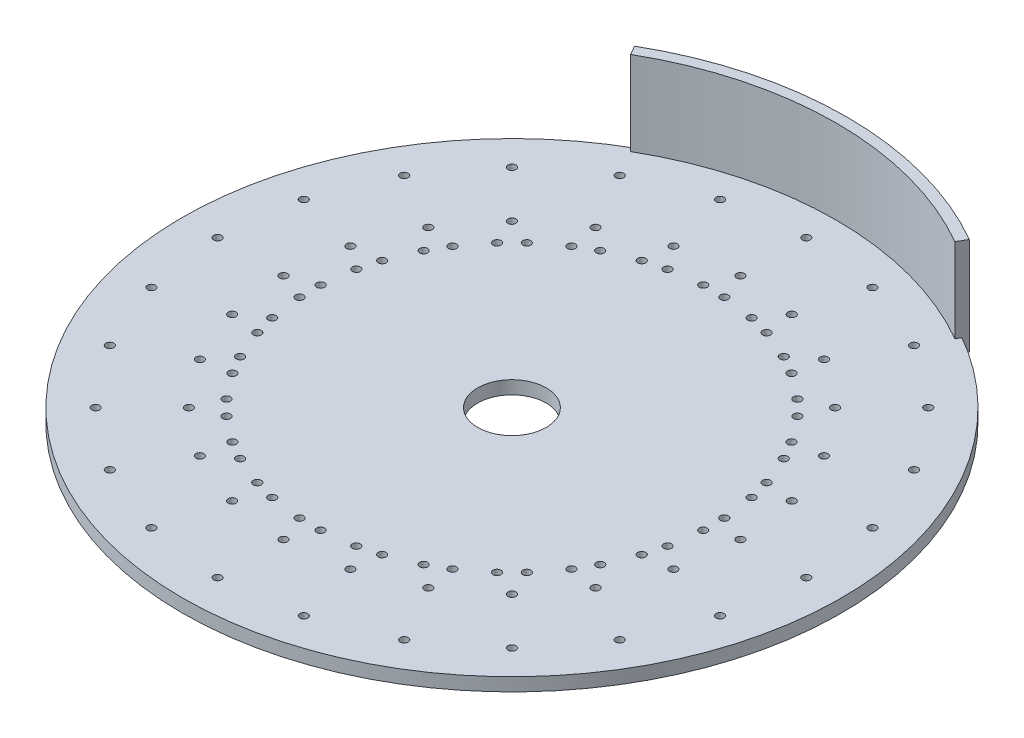
SolidWorks part; units mm, degrees
note: The reader was unsure of these and kept them because the rebuilt part matched: shared geometry of "Sketch2<3>".
material "ABS PC"
ref_plane "Front Plane" through (0, 0, 0) normal (0, 0, 1) x (1, 0, 0)
ref_plane "Top Plane" through (0, 0, 0) normal (0, 1, 0) x (1, 0, 0)
ref_plane "Right Plane" through (0, 0, 0) normal (1, 0, 0) x (0, 0, -1)
sketch "Sketch1" plane through (0, 0, 0) normal (0, 1, 0) x (1, 0, 0)
  line L0 (0, 0) -> (0, 145.2031) construction
  line L1 (0, 0) -> (86.65, 0) construction
  circle A0 centre (0, 0) radius 125
  circle A1 centre (0, 0) radius 76.652 construction
  circle A2 centre (0, 76.652) radius 2.5 construction
  circle A3 centre (21.001, 74.9318) radius 2.5 construction
  circle A4 centre (40.8412, 67.8347) radius 2.5 construction
  circle A5 centre (58.1686, 55.8445) radius 2.5 construction
  circle A6 centre (71.8022, 39.7782) radius 2.5 construction
  circle A7 centre (80.813, 20.7307) radius 2.5 construction
  circle A8 centre (84.5868, 0) radius 2.5 construction
  circle A9 centre (82.8667, -21.001) radius 2.5 construction
  circle A10 centre (75.7696, -40.8412) radius 2.5 construction
  circle A11 centre (63.7794, -58.1686) radius 2.5 construction
  circle A12 centre (47.713, -71.8022) radius 2.5 construction
  circle A13 centre (28.6655, -80.813) radius 2.5 construction
  circle A14 centre (7.9349, -84.5868) radius 2.5 construction
  circle A15 centre (-13.0662, -82.8667) radius 2.5 construction
  circle A16 centre (-32.9064, -75.7696) radius 2.5 construction
  circle A17 centre (-50.2337, -63.7794) radius 2.5 construction
  circle A18 centre (-63.8673, -47.713) radius 2.5 construction
  circle A19 centre (-72.8781, -28.6655) radius 2.5 construction
  circle A20 centre (-76.652, -7.9349) radius 2.5 construction
  circle A21 centre (-74.9318, 13.0662) radius 2.5 construction
  circle A22 centre (-67.8347, 32.9064) radius 2.5 construction
  circle A23 centre (-55.8445, 50.2337) radius 2.5 construction
  circle A24 centre (-39.7782, 63.8673) radius 2.5 construction
  circle A25 centre (-20.7307, 72.8781) radius 2.5 construction
  circle A26 centre (-4, 76.5475) radius 1.5
  circle A27 centre (4, 76.5475) radius 1.5
  circle A28 centre (15.9483, 74.9745) radius 1.5
  circle A29 centre (23.6757, 72.904) radius 1.5
  circle A30 centre (34.8097, 68.2921) radius 1.5
  circle A31 centre (41.7379, 64.2921) radius 1.5
  circle A32 centre (51.2989, 56.9557) radius 1.5
  circle A33 centre (56.9557, 51.2989) radius 1.5
  circle A34 centre (64.2921, 41.7379) radius 1.5
  circle A35 centre (68.2921, 34.8097) radius 1.5
  circle A36 centre (72.904, 23.6757) radius 1.5
  circle A37 centre (74.9745, 15.9483) radius 1.5
  circle A38 centre (76.5475, 4) radius 1.5
  circle A39 centre (76.5475, -4) radius 1.5
  circle A40 centre (74.9745, -15.9483) radius 1.5
  circle A41 centre (72.904, -23.6757) radius 1.5
  circle A42 centre (68.2921, -34.8097) radius 1.5
  circle A43 centre (64.2921, -41.7379) radius 1.5
  circle A44 centre (56.9557, -51.2989) radius 1.5
  circle A45 centre (51.2989, -56.9557) radius 1.5
  circle A46 centre (41.7379, -64.2921) radius 1.5
  circle A47 centre (34.8097, -68.2921) radius 1.5
  circle A48 centre (23.6757, -72.904) radius 1.5
  circle A49 centre (15.9483, -74.9745) radius 1.5
  circle A50 centre (4, -76.5475) radius 1.5
  circle A51 centre (-4, -76.5475) radius 1.5
  circle A52 centre (-15.9483, -74.9745) radius 1.5
  circle A53 centre (-23.6757, -72.904) radius 1.5
  circle A54 centre (-34.8097, -68.2921) radius 1.5
  circle A55 centre (-41.7379, -64.2921) radius 1.5
  circle A56 centre (-51.2989, -56.9557) radius 1.5
  circle A57 centre (-56.9557, -51.2989) radius 1.5
  circle A58 centre (-64.2921, -41.7379) radius 1.5
  circle A59 centre (-68.2921, -34.8097) radius 1.5
  circle A60 centre (-72.904, -23.6757) radius 1.5
  circle A61 centre (-74.9745, -15.9483) radius 1.5
  circle A62 centre (-76.5475, -4) radius 1.5
  circle A63 centre (-76.5475, 4) radius 1.5
  circle A64 centre (-74.9745, 15.9483) radius 1.5
  circle A65 centre (-72.904, 23.6757) radius 1.5
  circle A66 centre (-68.2921, 34.8097) radius 1.5
  circle A67 centre (-64.2921, 41.7379) radius 1.5
  circle A68 centre (-56.9557, 51.2989) radius 1.5
  circle A69 centre (-51.2989, 56.9557) radius 1.5
  circle A70 centre (-41.7379, 64.2921) radius 1.5
  circle A71 centre (-34.8097, 68.2921) radius 1.5
  circle A72 centre (-23.6757, 72.904) radius 1.5
  circle A73 centre (-15.9483, 74.9745) radius 1.5
  circle A74 centre (0, 0) radius 13
  circle A75 centre (86.65, 0) radius 1.5
  circle A76 centre (111.65, 0) radius 1.5
  circle A77 centre (107.8456, -28.8971) radius 1.5
  circle A78 centre (96.6917, -55.825) radius 1.5
  circle A79 centre (78.9485, -78.9485) radius 1.5
  circle A80 centre (55.825, -96.6917) radius 1.5
  circle A81 centre (28.8971, -107.8456) radius 1.5
  circle A82 centre (0, -111.65) radius 1.5
  circle A83 centre (-28.8971, -107.8456) radius 1.5
  circle A84 centre (-55.825, -96.6917) radius 1.5
  circle A85 centre (-78.9485, -78.9485) radius 1.5
  circle A86 centre (-96.6917, -55.825) radius 1.5
  circle A87 centre (-107.8456, -28.8971) radius 1.5
  circle A88 centre (-111.65, 0) radius 1.5
  circle A89 centre (-107.8456, 28.8971) radius 1.5
  circle A90 centre (-96.6917, 55.825) radius 1.5
  circle A91 centre (-78.9485, 78.9485) radius 1.5
  circle A92 centre (-55.825, 96.6917) radius 1.5
  circle A93 centre (-28.8971, 107.8456) radius 1.5
  circle A94 centre (0, 111.65) radius 1.5
  circle A95 centre (28.8971, 107.8456) radius 1.5
  circle A96 centre (55.825, 96.6917) radius 1.5
  circle A97 centre (78.9485, 78.9485) radius 1.5
  circle A98 centre (96.6917, 55.825) radius 1.5
  circle A99 centre (107.8456, 28.8971) radius 1.5
  circle A100 centre (0, 0) radius 111.65 construction
  circle A101 centre (0, 0) radius 81.1 construction
  circle A103 centre (83.6975, -22.4267) radius 1.5
  circle A104 centre (75.0411, -43.325) radius 1.5
  circle A105 centre (61.2708, -61.2708) radius 1.5
  circle A106 centre (43.325, -75.0411) radius 1.5
  circle A107 centre (22.4267, -83.6975) radius 1.5
  circle A108 centre (0, -86.65) radius 1.5
  circle A109 centre (-22.4267, -83.6975) radius 1.5
  circle A110 centre (-43.325, -75.0411) radius 1.5
  circle A111 centre (-61.2708, -61.2708) radius 1.5
  circle A112 centre (-75.0411, -43.325) radius 1.5
  circle A113 centre (-83.6975, -22.4267) radius 1.5
  circle A114 centre (-86.65, 0) radius 1.5
  circle A115 centre (-83.6975, 22.4267) radius 1.5
  circle A116 centre (-75.0411, 43.325) radius 1.5
  circle A117 centre (-61.2708, 61.2708) radius 1.5
  circle A118 centre (-43.325, 75.0411) radius 1.5
  circle A119 centre (-22.4267, 83.6975) radius 1.5
  circle A120 centre (0, 86.65) radius 1.5
  circle A121 centre (22.4267, 83.6975) radius 1.5
  circle A122 centre (43.325, 75.0411) radius 1.5
  circle A123 centre (61.2708, 61.2708) radius 1.5
  circle A124 centre (75.0411, 43.325) radius 1.5
  circle A125 centre (83.6975, 22.4267) radius 1.5
  circle A126 centre (0, 222.5) radius 5 construction
  circle A127 centre (192.6907, 111.25) radius 5 construction
  circle A128 centre (192.6907, -111.25) radius 5 construction
  circle A129 centre (0, -222.5) radius 5 construction
  circle A130 centre (-192.6907, -111.25) radius 5 construction
  circle A131 centre (-192.6907, 111.25) radius 5 construction
  point P55 (3.9674, -3.9674)
  point P152 (0, 0)
  point P205 (0, 0)
  point P265 (0, 0)
  dimension "D1" = 250
  dimension "D2" = 5
  dimension "D4" = 8
  dimension "D5" = 3
  dimension "D7" = 26
  dimension "D8" = 86.65
  dimension "D9" = 3
  dimension "D10" = 222.5
  dimension "D11" = 24
  dimension "D12" = 223.3
  dimension "D13" = 162.2
  dimension "D14" = 10
  dimension "D3" = 24
  dimension "D6" = 24
  dimension "D15" = 6
extrude "Boss-Extrude1" add sketch "Sketch1" along normal mid plane 5
sketch "Sketch2" plane through (0, 2.5, 0) normal (0, 1, 0) x (1, 0, 0)
  line L0 (0, 0) -> (0, 134.0877) construction
  line L1 (-63.5, 109.9852) -> (-61.5, 106.5211)
  line L2 (61.5, 106.5211) -> (63.5, 109.9852)
  line L3 (-61.5, 106.5211) -> (0, 0) construction
  line L4 (0, 0) -> (61.5, 106.5211) construction
  arc A0 (-62.5, 108.2532) -> (62.5, 108.2532) centre (0, 0) cw
  circle A1 centre (0, 0) radius 125 construction
  arc A2 (-61.5, 106.5211) -> (61.5, 106.5211) centre (0, 0) cw
  arc A3 (-63.5, 109.9852) -> (63.5, 109.9852) centre (0, 0) cw
  dimension "D1" = 60
  dimension "D2" = 2
  dimension "D3" = 2
extrude "Boss-Extrude2" add sketch "Sketch2" against normal blind 5 and the other way blind 32 separate body contours A3 L1 A0 L2
extrude "Boss-Extrude3" add sketch "Sketch2<3>" along direction (0, 1, 0) on the side of the normal up to surface (31.9 mm away) from offset 0.1 contours L1 A2 L2 A0
sketch "Sketch2<3>" plane through (0, 2.5, 0) normal (0, 1, 0) x (1, 0, 0) same geometry as "Sketch2"
split "Split1" bodies to split 133 101 resulting bodies 134 135 split by face at (0, 2.5, 125)
